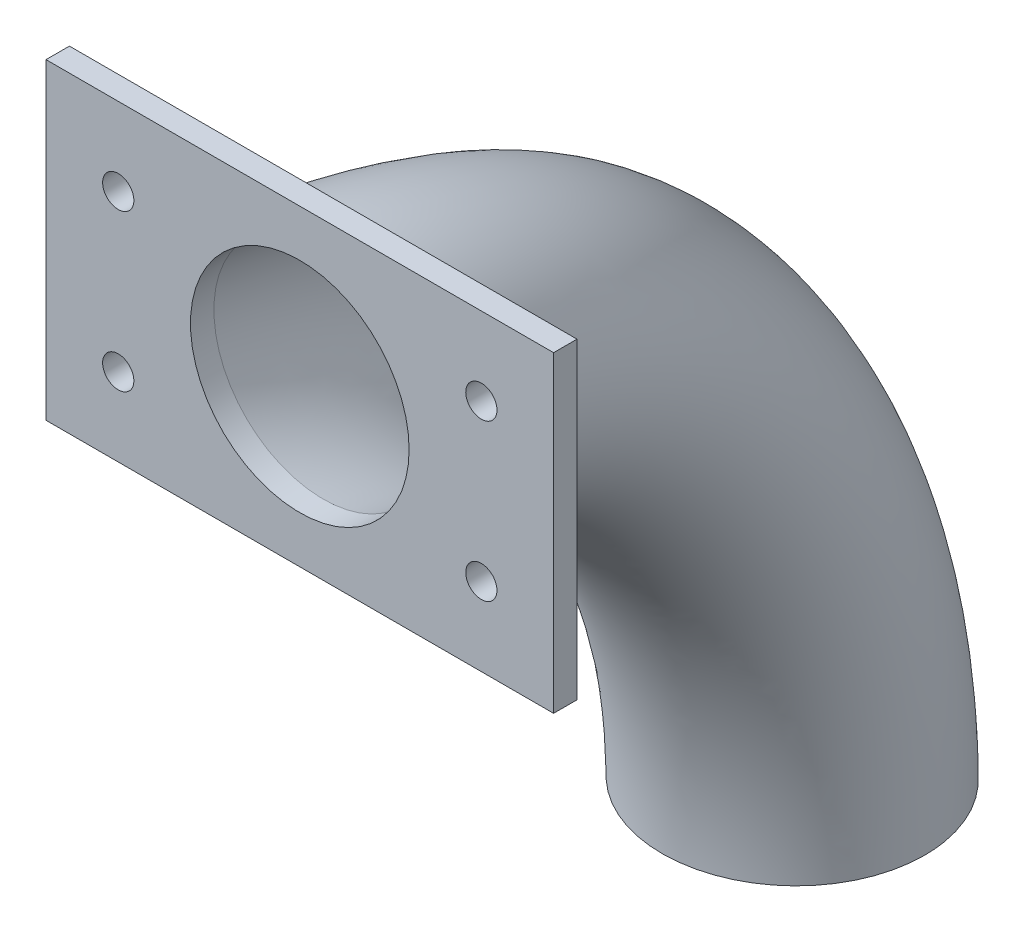
SolidWorks part; units mm, degrees
ref_plane "Plan de face" through (0, 0, 0) normal (0, 0, 1) x (1, 0, 0)
ref_plane "Plan de dessus" through (0, 0, 0) normal (0, 1, 0) x (1, 0, 0)
ref_plane "Plan de droite" through (0, 0, 0) normal (1, 0, 0) x (0, 0, -1)
sketch "Esquisse1" plane through (0, 0, 0) normal (0, 0, 1) x (1, 0, 0)
  circle A0 centre (0, 0) radius 14
  circle A1 centre (0, 0) radius 17
  dimension "D1" = 28
  dimension "D2" = 3
sketch "Esquisse2" plane through (0, 0, 0) normal (1, 0, 0) x (0, 0, -1)
  line L0 (0, 0) -> (0, -78) construction
  line L1 (0, -78) -> (60, -78) construction
  spline S0 degree 3 poles (0, 0) (10.1586, -1.9182) (29.5002, -7.7954) (53.7994, -35.8324) (60.4325, -61.4407) (60, -78) knots 0 0 0 0 0.290143 0.539445 1 1 1 1
  point P4 (29.1613, -10.9155)
  point P6 (27.6589, -10.0808)
  point P8 (49.3599, -34.9535)
  point P10 (58.2072, -57.9899)
  point P12 (47.3567, -30.6133)
  dimension "D1" = 78
  dimension "D2" = 60
sweep "Balayage1" add profiles "Esquisse1" path "Esquisse2"
ref_plane "Plan1" through (0, -75, 0) normal (0, 1, 0) x (1, 0, 0)
sketch "Esquisse3" plane through (0, -75, 0) normal (0, 1, 0) x (1, 0, 0)
  line L1 (35.0227, 91.4102) -> (-35.0227, 91.4102)
  line L2 (35.0227, 91.4102) -> (35.0227, 31.3519)
  line L3 (35.0227, 31.3519) -> (-35.0227, 31.3519)
  line L4 (-35.0227, 91.4102) -> (-35.0227, 31.3519)
  line L5 (35.0227, 91.4102) -> (-35.0227, 31.3519) construction
  line L6 (35.0227, 31.3519) -> (-35.0227, 91.4102) construction
  point P0 (0, 61.381)
extrude "Enlèv. mat.-Extru.1" cut sketch "Esquisse3" against normal blind 10
sketch "Esquisse4" plane through (0, 0, 0) normal (0, 0, 1) x (1, 0, 0)
  line L0 (-14, 0) -> (-32.5, 0) construction
  line L1 (-32.5, -20) -> (32.5, -20)
  line L2 (-32.5, -20) -> (-32.5, 20)
  line L3 (-32.5, 20) -> (32.5, 20)
  line L4 (32.5, -20) -> (32.5, 20)
  line L5 (-32.5, -20) -> (32.5, 20) construction
  line L6 (-32.5, 20) -> (32.5, -20) construction
  line L7 (-23.25, 0) -> (-23.25, 20) construction
  line L8 (0, 20) -> (0, -20) construction
  circle A0 centre (0, 0) radius 14
  circle A1 centre (-23.25, 10) radius 2
  circle A2 centre (-23.25, -10) radius 2
  circle A3 centre (23.25, -10) radius 2
  circle A4 centre (23.25, 10) radius 2
  point P0 (0, 0)
  dimension "D3" = 4
  dimension "D4" = 9.25
  dimension "D1" = 65
  dimension "D2" = 40
extrude "Boss.-Extru.1" add sketch "Esquisse4" along normal blind 3
